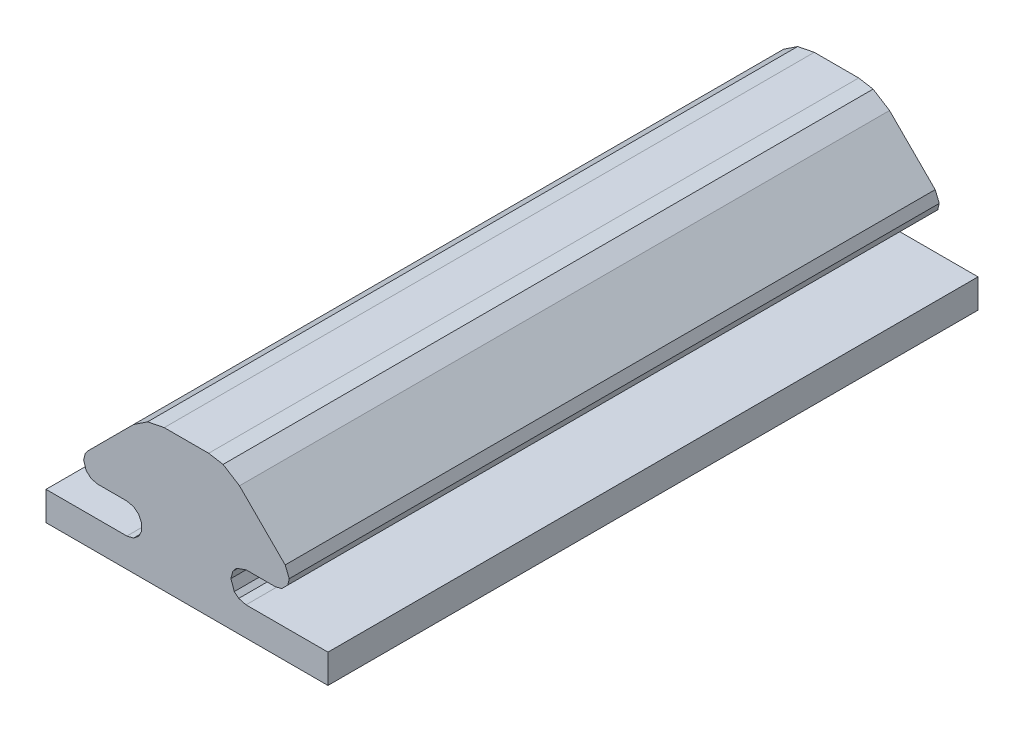
SolidWorks part; units mm, degrees
ref_plane "Front Plane" through (0, 0, 0) normal (0, 0, 1) x (1, 0, 0)
ref_plane "Top Plane" through (0, 0, 0) normal (0, 1, 0) x (1, 0, 0)
ref_plane "Right Plane" through (0, 0, 0) normal (1, 0, 0) x (0, 0, -1)
sketch "Sketch5" plane through (0, 0, 0) normal (0, 0, 1) x (1, 0, 0)
  line L0 (-6.4748, -10.4902) -> (-6.9383, -10.3783)
  line L1 (-6.9383, -10.3783) -> (-7.3088, -10.0545)
  line L2 (-7.3088, -10.0545) -> (-7.4908, -9.4742)
  line L3 (-7.4908, -9.4742) -> (-7.3789, -9.0107)
  line L4 (-7.3789, -9.0107) -> (-7.1932, -8.7558)
  line L5 (-7.1932, -8.7558) -> (-3.8632, -5.4257)
  line L6 (-3.8632, -5.4257) -> (-2.8331, -4.7375)
  line L7 (-2.8331, -4.7375) -> (-1.6181, -4.4958)
  line L8 (-1.6181, -4.4958) -> (1.6181, -4.4958)
  line L9 (1.6181, -4.4958) -> (2.6682, -4.6745)
  line L10 (2.6682, -4.6745) -> (3.8632, -5.4257)
  line L11 (3.8632, -5.4257) -> (7.1932, -8.7558)
  line L12 (7.1932, -8.7558) -> (7.4908, -9.4742)
  line L13 (7.4908, -9.4742) -> (7.3789, -9.9377)
  line L14 (6.4748, -10.4902) -> (6.9383, -10.3783)
  line L15 (6.9383, -10.3783) -> (7.3789, -9.9377)
  line L16 (6.4748, -10.4902) -> (4.3434, -10.4902)
  line L19 (-6.4748, -10.4902) -> (-4.3434, -10.4902)
  line L20 (-4.3434, -10.4902) -> (-3.8632, -10.6)
  line L21 (-3.8632, -10.6) -> (-3.486, -10.8982)
  line L22 (-3.486, -10.8982) -> (-3.2711, -11.3288)
  line L23 (-3.2711, -11.3288) -> (-3.2711, -11.8614)
  line L24 (-3.2711, -11.8614) -> (-3.486, -12.292)
  line L25 (-3.486, -12.292) -> (-3.8632, -12.5902)
  line L26 (-3.8632, -12.5902) -> (-4.3434, -12.7)
  line L27 (-4.3434, -12.7) -> (-9.5504, -12.7)
  line L28 (-9.5504, -12.7) -> (-9.5504, -18.9956)
  line L29 (-9.5504, -18.9956) -> (10.5918, -18.9956)
  line L30 (10.5918, -18.9956) -> (10.5918, -12.7)
  line L31 (10.5918, -12.7) -> (4.3434, -12.7)
  line L32 (4.3434, -12.7) -> (3.8076, -12.5614)
  line L33 (3.8076, -12.5614) -> (3.486, -12.292)
  line L34 (3.486, -12.292) -> (3.2385, -11.5951)
  line L35 (3.2385, -11.5951) -> (3.3771, -11.0593)
  line L36 (3.3771, -11.0593) -> (3.6465, -10.7377)
  line L37 (3.6465, -10.7377) -> (4.3434, -10.4902)
extrude "Boss-Extrude1" add sketch "Sketch5" against normal blind 47.371
sketch "Sketch18" plane through (0, -18.9956, 0) normal (0, -1, 0) x (1, 0, 0)
  line L1 (-9.5504, -47.371) -> (10.5918, -47.371)
  line L2 (-9.5504, -47.371) -> (-9.5504, 0)
  line L3 (-9.5504, 0) -> (10.5918, 0)
  line L4 (10.5918, -47.371) -> (10.5918, 0)
extrude "Cut-Extrude8" cut sketch "Sketch18" against normal blind 2.286
sketch "Sketch20" plane through (10.5918, 0, 0) normal (1, 0, 0) x (0, 0, -1)
  line L1 (47.371, -16.7096) -> (-0.0343, -16.7096)
  line L2 (47.371, -16.7096) -> (47.371, -12.7)
  line L3 (47.371, -12.7) -> (-0.0343, -12.7)
  line L4 (-0.0343, -16.7096) -> (-0.0343, -12.7)
extrude "Cut-Extrude9" cut sketch "Sketch20" against normal blind 0.2794
sketch "Sketch21" plane through (-9.5504, 0, 0) normal (-1, 0, 0) x (0, 0, 1)
  line L1 (-47.371, -12.7) -> (0, -12.7)
  line L2 (-47.371, -12.7) -> (-47.371, -16.7096)
  line L3 (-47.371, -16.7096) -> (0, -16.7096)
  line L4 (0, -12.7) -> (0, -16.7096)
extrude "Boss-Extrude2" add sketch "Sketch21" along normal blind 0.6858
sketch "Sketch23" plane through (0, -16.7096, 0) normal (0, -1, 0) x (1, 0, 0)
  line L1 (10.3124, -47.371) -> (-10.2362, -47.371)
  line L2 (10.3124, -47.371) -> (10.3124, 0)
  line L3 (10.3124, 0) -> (-10.2362, 0)
  line L4 (-10.2362, -47.371) -> (-10.2362, 0)
extrude "Cut-Extrude11" cut sketch "Sketch23" against normal blind 1.905
sketch "Sketch24" plane through (0, 0, 0) normal (0, 0, 1) x (1, 0, 0)
  line L0 (-4.3434, -12.7) -> (-3.2711, -12.7)
  line L1 (-3.2711, -12.7) -> (-3.2711, -10.4902)
  line L2 (-3.2711, -10.4902) -> (-7.4908, -10.4902)
  line L3 (-7.4908, -10.4902) -> (-7.4908, -9.0272)
  line L4 (-7.4908, -9.0272) -> (-2.9912, -4.5045)
  line L5 (-2.9912, -4.5045) -> (2.9934, -4.5045)
  line L6 (4.3434, -12.7) -> (3.2385, -12.7)
  line L7 (3.2385, -12.7) -> (3.2385, -10.4902)
  line L8 (3.2385, -10.4902) -> (7.4908, -10.4902)
  line L9 (7.4908, -10.4902) -> (7.4908, -9.0272)
  line L10 (7.4908, -9.0272) -> (2.9934, -4.5045)
  point P16 (2.9934, -4.5045)
